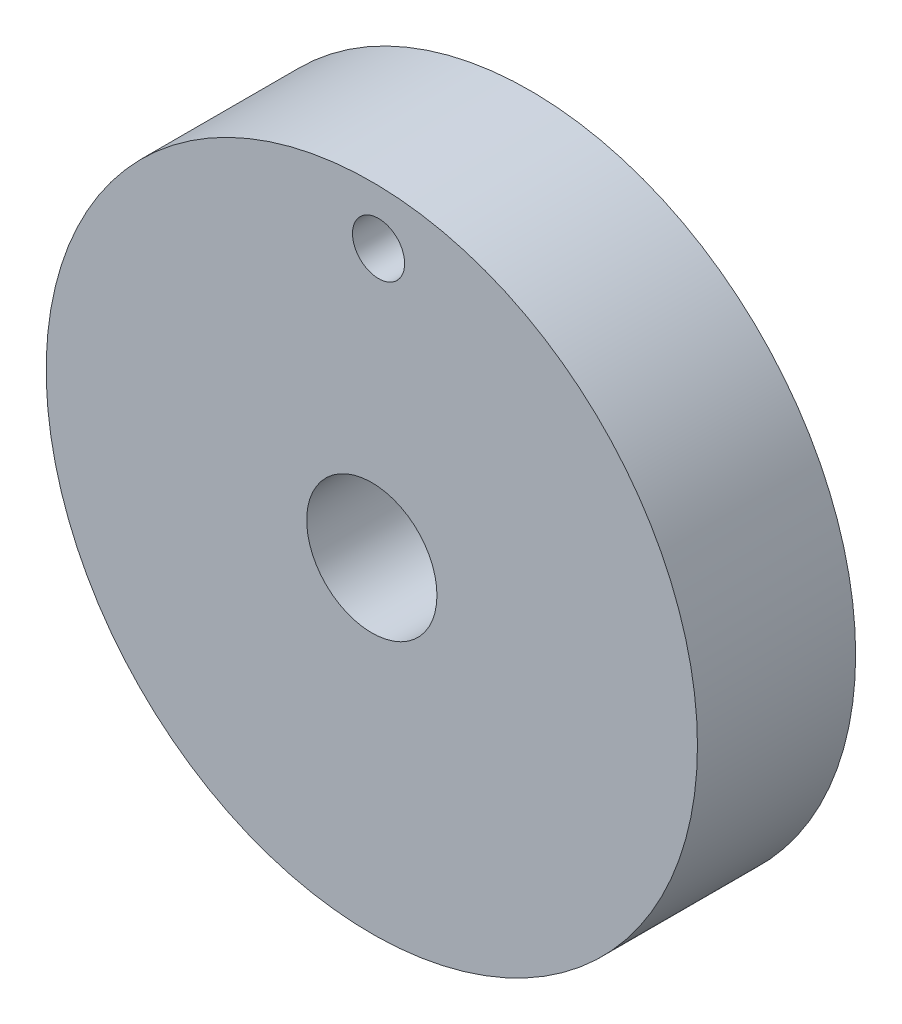
SolidWorks part; units mm, degrees
ref_plane "Front Plane" through (0, 0, 0) normal (0, 0, 1) x (1, 0, 0)
ref_plane "Top Plane" through (0, 0, 0) normal (0, 1, 0) x (1, 0, 0)
ref_plane "Right Plane" through (0, 0, 0) normal (1, 0, 0) x (0, 0, -1)
sketch "Sketch1" plane through (0, 0, 0) normal (0, 0, 1) x (1, 0, 0)
  circle A0 centre (0, 0) radius 18
extrude "Boss-Extrude1" add sketch "Sketch1" along normal blind 20
sketch "Sketch2" plane through (0, 0, 20) normal (0, 0, 1) x (1, 0, 0)
  circle A0 centre (0, 0) radius 7
extrude "Cut-Extrude1" cut sketch "Sketch2" against normal blind 60
sketch "Sketch4" plane through (0, 0, 20) normal (0, 0, 1) x (1, 0, 0)
  circle A0 centre (0, 0) radius 14.576
  circle A1 centre (0, 0) radius 35
extrude "Boss-Extrude2" add sketch "Sketch4" against normal blind 17
sketch "Sketch5" plane through (0, 0, 20) normal (0, 0, 1) x (1, 0, 0)
  circle A0 centre (0.7243, 29.1419) radius 2.8029
extrude "Cut-Extrude2" cut sketch "Sketch5" against normal blind 4
